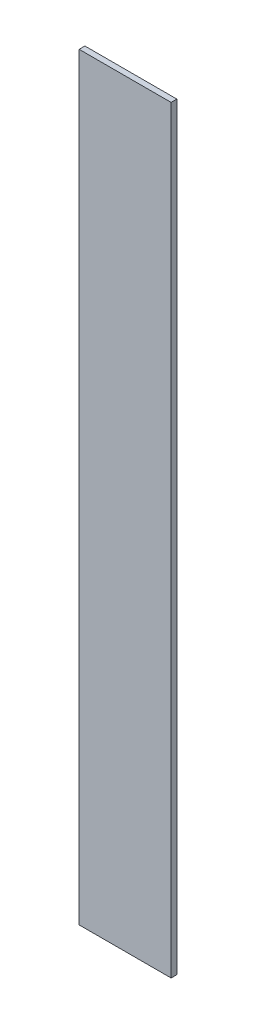
SolidWorks part; units mm, degrees
ref_plane "Front Plane" through (0, 0, 0) normal (0, 0, 1) x (1, 0, 0)
ref_plane "Top Plane" through (0, 0, 0) normal (0, 1, 0) x (1, 0, 0)
ref_plane "Right Plane" through (0, 0, 0) normal (1, 0, 0) x (0, 0, -1)
sketch "Sketch1" plane through (0, 0, 0) normal (0, 0, 1) x (1, 0, 0)
  line L1 (0, 0) -> (25.4, 0)
  line L2 (0, 0) -> (0, 209.55)
  line L3 (0, 209.55) -> (25.4, 209.55)
  line L4 (25.4, 0) -> (25.4, 209.55)
  dimension "D1" = 209.55
  dimension "D2" = 25.4
extrude "Boss-Extrude1" add sketch "Sketch1" along normal blind 1.5875
